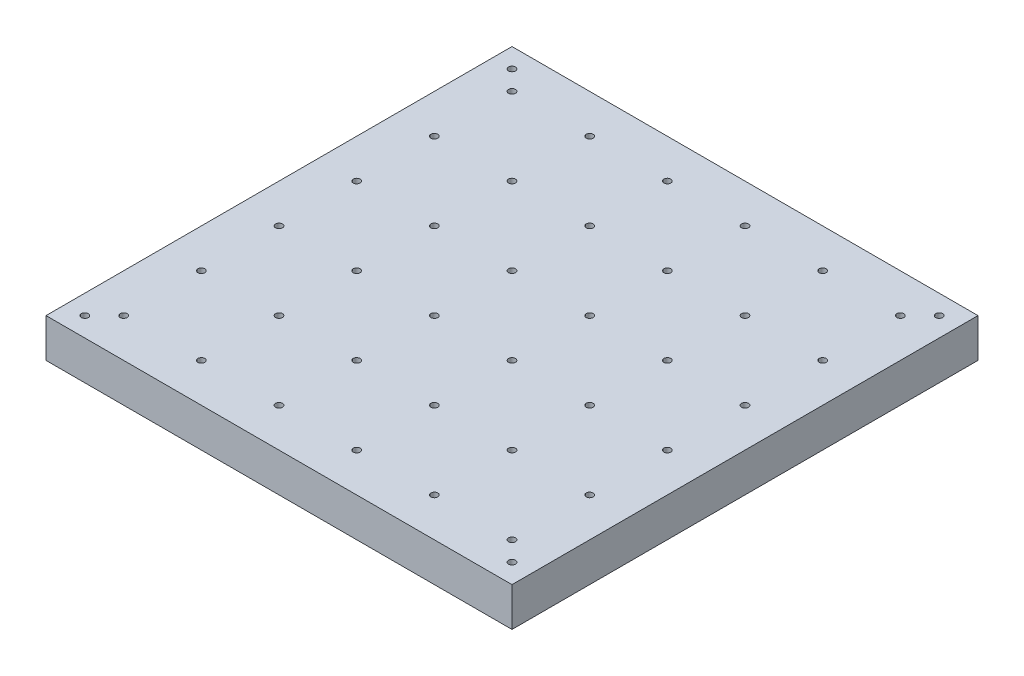
SolidWorks part; units mm, degrees
ref_plane "Front Plane" through (0, 0, 0) normal (0, 0, 1) x (1, 0, 0)
ref_plane "Top Plane" through (0, 0, 0) normal (0, 1, 0) x (1, 0, 0)
ref_plane "Right Plane" through (0, 0, 0) normal (1, 0, 0) x (0, 0, -1)
sketch "Sketch1" plane through (0, 0, 0) normal (0, 1, 0) x (1, 0, 0)
  line L1 (-76.2, 76.2) -> (76.2, 76.2)
  line L2 (-76.2, 76.2) -> (-76.2, -76.2)
  line L3 (-76.2, -76.2) -> (76.2, -76.2)
  line L4 (76.2, 76.2) -> (76.2, -76.2)
  line L5 (-76.2, 76.2) -> (76.2, -76.2) construction
  line L6 (-76.2, -76.2) -> (76.2, 76.2) construction
  circle A1 centre (-46.2, 46.2) radius 15.875
  point P0 (0, 0)
  dimension "D2" = 31.75
  dimension "D1" = 152.4
  dimension "D3" = 30
  dimension "D4" = 30
extrude "Boss-Extrude1" add sketch "Sketch1" along normal blind 12.7 contours A1 | L4 L1 L2 L3 A1 region at (1.6305, 0, 1.6305) region at (-46.2, 0, -46.2)
hole_wizard "#4-40 Tapped Hole1" positions "3DSketch1" profile "Sketch2" tap size "#4-40" standard "ANSI Inch" end condition through all
sketch3d "3DSketch1"
  line L2 (-76.2, 12.7, 76.2) -> (76.2, 12.7, 76.2) construction
  line L3 (76.2, 12.7, -76.2) -> (76.2, 12.7, 76.2) construction
  point P0 (69.85, 12.7, 69.85)
  point P11 (0, 0, 0)
  point P12 (0, 0, 0)
  dimension "D1" = 6.35
  dimension "D2" = 6.35
cosmetic thread "Hole Thread1" parameters "D2"=2.8448
sketch "Sketch2" plane through (69.85, 12.7, 69.85) normal (1, 0, 0) x (0, 0, 1)
  line L0 (0, 0) -> (0, 12.7)
  line L1 (0, 12.7) -> (1.1303, 12.7)
  line L2 (1.1303, 12.7) -> (1.1303, 0)
  line L5 (1.1303, 0) -> (0, 0)
  line L11 (0, -6.35) -> (0, 107.95) construction
  dimension "Thru Tap Drill Dia." = 2.2606
  dimension "Thru Tap Drill Depth" = 12.7
pattern_linear "LPattern1" count 2 spacing 139.7 along (0, 0, -1) count 2 spacing 139.7 along (-1, 0, 0) of "#4-40 Tapped Hole1"
cosmetic thread "Hole Thread2"
cosmetic thread "Hole Thread3"
cosmetic thread "Hole Thread4"
hole_wizard "#4-40 Tapped Hole2" positions "3DSketch2" profile "Sketch3" tap size "#4-40" standard "ANSI Inch" end condition through all
sketch3d "3DSketch2"
  line L2 (76.2, 12.7, -76.2) -> (76.2, 12.7, 76.2) construction
  line L3 (-76.2, 12.7, 76.2) -> (76.2, 12.7, 76.2) construction
  point P0 (63.5, 12.7, 63.5)
  point P7 (0, 0, 0)
  point P8 (0, 0, 0)
  point P13 (0, 0, 0)
  dimension "D1" = 12.7
  dimension "D2" = 12.7
sketch "Sketch3" plane through (63.5, 12.7, 63.5) normal (1, 0, 0) x (0, 0, 1)
  line L0 (0, 0) -> (0, 12.7)
  line L1 (0, 12.7) -> (1.1303, 12.7)
  line L2 (1.1303, 12.7) -> (1.1303, 0)
  line L5 (1.1303, 0) -> (0, 0)
  line L11 (0, -6.35) -> (0, 107.95) construction
  dimension "Thru Tap Drill Dia." = 2.2606
  dimension "Thru Tap Drill Depth" = 12.7
cosmetic thread "Hole Thread5"
pattern_linear "LPattern2" count 6 spacing 25.4 along (0, 0, -1) count 6 spacing 25.4 along (-1, 0, 0) of "#4-40 Tapped Hole2"
cosmetic thread "Hole Thread6"
cosmetic thread "Hole Thread7"
cosmetic thread "Hole Thread8"
cosmetic thread "Hole Thread9"
cosmetic thread "Hole Thread10"
cosmetic thread "Hole Thread11"
cosmetic thread "Hole Thread12"
cosmetic thread "Hole Thread13"
cosmetic thread "Hole Thread14"
cosmetic thread "Hole Thread15"
cosmetic thread "Hole Thread16"
cosmetic thread "Hole Thread17"
cosmetic thread "Hole Thread18"
cosmetic thread "Hole Thread19"
cosmetic thread "Hole Thread20"
cosmetic thread "Hole Thread21"
cosmetic thread "Hole Thread22"
cosmetic thread "Hole Thread23"
cosmetic thread "Hole Thread24"
cosmetic thread "Hole Thread25"
cosmetic thread "Hole Thread26"
cosmetic thread "Hole Thread27"
cosmetic thread "Hole Thread28"
cosmetic thread "Hole Thread29"
cosmetic thread "Hole Thread30"
cosmetic thread "Hole Thread31"
cosmetic thread "Hole Thread32"
cosmetic thread "Hole Thread33"
cosmetic thread "Hole Thread34"
cosmetic thread "Hole Thread35"
cosmetic thread "Hole Thread36"
cosmetic thread "Hole Thread37"
cosmetic thread "Hole Thread38"
cosmetic thread "Hole Thread39"
cosmetic thread "Hole Thread40"
ref_plane "Plane1" through (0, 12.7, 0) normal (0, 1, 0) x (1, 0, 0)
sketch "Sketch4" plane through (0, 12.7, 0) normal (0, 1, 0) x (1, 0, 0)
  line L0 (-76.2, 76.2) -> (76.2, 76.2) construction
  line L1 (-76.2, 76.2) -> (-76.2, -76.2) construction
  point P0 (-46.2, 46.2)
  dimension "D1" = 30
  dimension "D2" = 30
